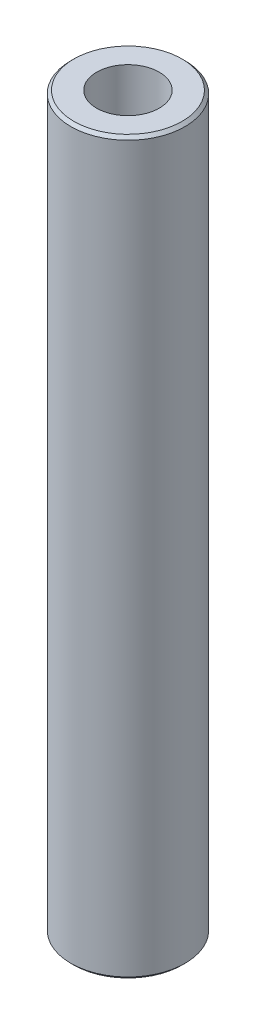
SolidWorks part; units mm, degrees
ref_plane "Front Plane" through (0, 0, 0) normal (0, 0, 1) x (1, 0, 0)
ref_plane "Top Plane" through (0, 0, 0) normal (0, 1, 0) x (1, 0, 0)
ref_plane "Right Plane" through (0, 0, 0) normal (1, 0, 0) x (0, 0, -1)
sketch "Sketch1" plane through (0, 0, 0) normal (0, 1, 0) x (1, 0, 0)
  circle A0 centre (0, 0) radius 7.5
  dimension "SHAFT_OD" = 15
extrude "Boss-Extrude1" add sketch "Sketch1" along normal blind 95.9496
sketch "Sketch2" plane through (0, 0, 0) normal (0, 1, 0) x (1, 0, 0)
  circle A0 centre (0, 0) radius 4.1076
  dimension "BORE_D" = 8.2152
extrude "Cut-Extrude1" cut sketch "Sketch2" along normal through all
chamfer "Chamfer1" distance 0.3954 angle 45 2 edges at (0, 95.9496, 7.5) (0, 0, 7.5)
